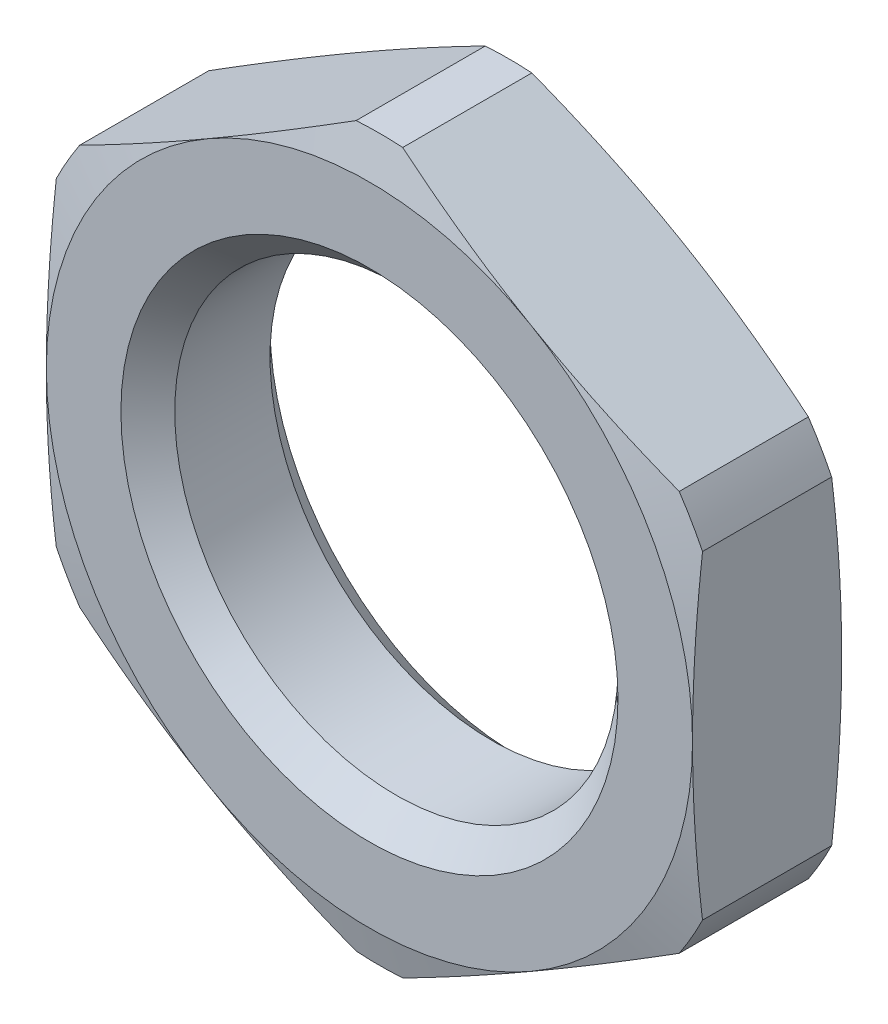
SolidWorks part; units mm, degrees
ref_plane "Ebene vorne" through (0, 0, 0) normal (0, 0, 1) x (1, 0, 0)
ref_plane "Ebene oben" through (0, 0, 0) normal (0, 1, 0) x (1, 0, 0)
ref_plane "Ebene rechts" through (0, 0, 0) normal (1, 0, 0) x (0, 0, -1)
sketch "Skizze1" plane through (0, 0, 0) normal (1, 0, 0) x (0, 0, -1)
  line L0 (-3, 6.5) -> (-3, 5)
  line L1 (-3, 5) -> (-2.4585, 4.4585)
  line L2 (-2.4585, 4.4585) -> (-0.5415, 4.4585)
  line L3 (-0.5415, 4.4585) -> (0, 5)
  line L4 (0, 5) -> (0, 6.5)
  line L5 (0, 6.5) -> (-0.201, 7.25)
  line L6 (-0.201, 7.25) -> (-2.799, 7.25)
  line L7 (-2.799, 7.25) -> (-3, 6.5)
  line L8 (0, 0) -> (-3, 0) construction
revolve "Rotation1" add sketch "Skizze1" angle 360 about L8 reverse direction yes
cosmetic thread "Gewindedarstellung1" parameters "D1"=3, "D2"=10
sketch "Skizze2" plane through (0, 0, 0) normal (0, 0, 1) x (1, 0, 0)
  line L0 (-36.5834, -35.5) -> (33.0833, -35.5)
  line L1 (33.0833, -35.5) -> (33.0833, 33.1667)
  line L2 (33.0833, 33.1667) -> (-36.5834, 33.1667)
  line L3 (-36.5834, 33.1667) -> (-36.5834, -35.5)
  line L4 (-6.5, -3.7528) -> (0, -7.5056)
  line L5 (0, -7.5056) -> (6.5, -3.7528)
  line L6 (6.5, -3.7528) -> (6.5, 3.7528)
  line L7 (6.5, 3.7528) -> (0, 7.5056)
  line L8 (0, 7.5056) -> (-6.5, 3.7528)
  line L9 (-6.5, 3.7528) -> (-6.5, -3.7528)
extrude "Schnitt-Linear austragen1" cut sketch "Skizze2" along normal blind 10 and the other way blind 10
ref_plane "mutter XY" through (0, 0, 0) normal (0, 0, 1) x (1, 0, 0)
ref_plane "mutter XZ" through (0, 0, 0) normal (0, -1, 0) x (-1, 0, 0)
ref_plane "mutter YZ" through (0, 0, 0) normal (1, 0, 0) x (0, 0, -1)
ref_axis "mutter X" through (-80.9, 0, 0) along (1, 0, 0)
ref_axis "mutter Y" through (0, -50, 0) along (0, 1, 0)
ref_axis "mutter Z" through (0, 0, 80.9) along (0, 0, -1)
sketch3d "mutter"
  point P0 (0, 0, 0)
